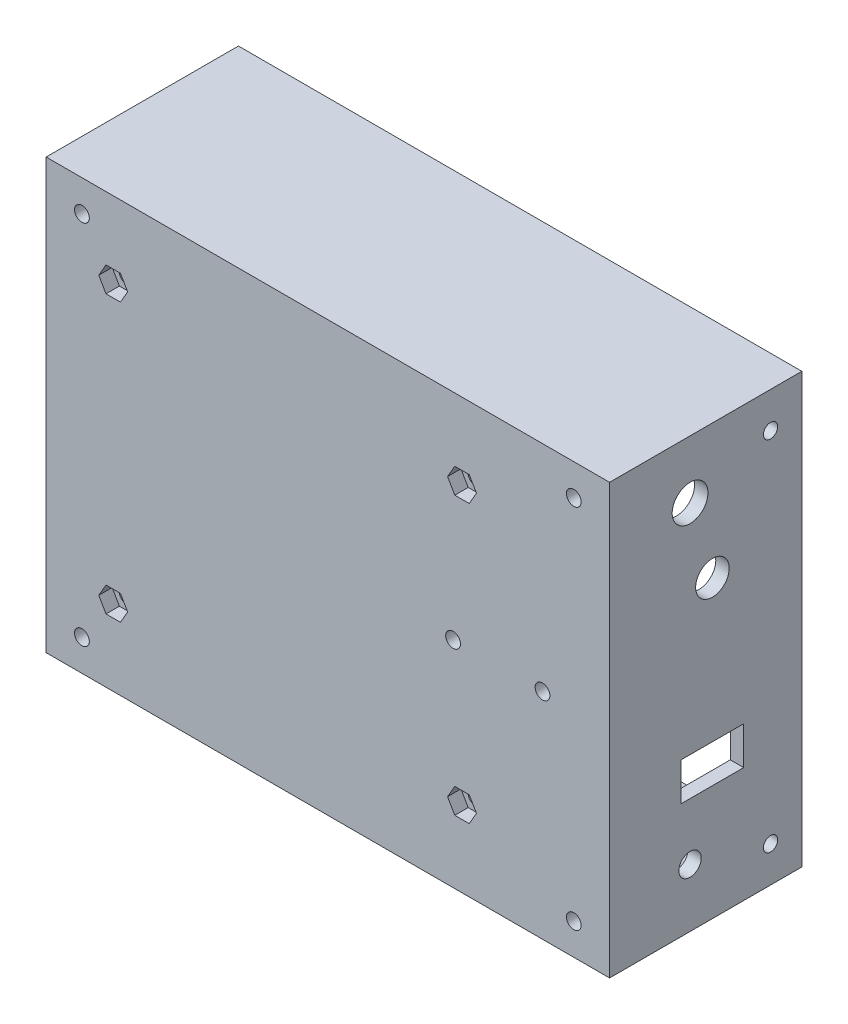
SolidWorks part; units mm, degrees
ref_plane "Front Plane" through (0, 0, 0) normal (0, 0, 1) x (1, 0, 0)
ref_plane "Top Plane" through (0, 0, 0) normal (0, 1, 0) x (1, 0, 0)
ref_plane "Right Plane" through (0, 0, 0) normal (1, 0, 0) x (0, 0, -1)
sketch "Sketch1" plane through (0, 0, 0) normal (0, 0, 1) x (1, 0, 0)
  line L1 (-60, -45) -> (60, -45)
  line L2 (-60, -45) -> (-60, 45)
  line L3 (-60, 45) -> (60, 45)
  line L4 (60, -45) -> (60, 45)
  line L5 (-60, -45) -> (60, 45) construction
  line L6 (-60, 45) -> (60, -45) construction
  line L7 (-48, -31) -> (30, -31)
  line L8 (-48, -31) -> (-48, 31)
  line L9 (-48, 31) -> (30, 31)
  line L10 (30, -31) -> (30, 31)
  line L11 (-48, -31) -> (30, 31) construction
  line L12 (-48, 31) -> (30, -31) construction
  circle A0 centre (-48, 31) radius 1.65
  circle A1 centre (30, 31) radius 1.65
  circle A2 centre (30, -31) radius 1.65
  circle A3 centre (-48, -31) radius 1.65
  circle A4 centre (-55, 41) radius 1.65
  circle A5 centre (55, 41) radius 1.65
  circle A6 centre (55, -41) radius 1.65
  circle A7 centre (-55, -41) radius 1.65
  point P0 (0, 0)
  point P6 (-9, 0)
  dimension "D7" = 3.3
  dimension "D8" = 4
  dimension "D9" = 5
  dimension "D10" = 5
  dimension "D11" = 4
  dimension "D12" = 3.3
  dimension "D13" = 5
  dimension "D14" = 4
  dimension "D15" = 4
  dimension "D16" = 5
  dimension "D1" = 90
  dimension "D2" = 120
  dimension "D3" = 62
  dimension "D4" = 78
  dimension "D5" = 14
  dimension "D6" = 30
extrude "Boss-Extrude2" add sketch "Sketch1" along normal blind 4 contours L1 L4 L3 L2 A3 L8 A0 L9 A1 L10 A2 L7 | A3 L7 A2 L10 A1 L9 A0 L8 region at (-58.5, 0, 0) region at (-9, 0, 0)
sketch "Sketch2" plane through (0, 0, 4) normal (0, 0, 1) x (1, 0, 0)
  line L1 (60, -45) -> (-60, -45)
  line L2 (60, -45) -> (60, 45)
  line L3 (60, 45) -> (-60, 45)
  line L4 (-60, -45) -> (-60, 45)
  line L5 (60, -45) -> (-60, 45) construction
  line L6 (60, 45) -> (-60, -45) construction
  line L7 (63, -48) -> (-63, -48)
  line L8 (63, -48) -> (63, 48)
  line L9 (63, 48) -> (-63, 48)
  line L10 (-63, -48) -> (-63, 48)
  line L11 (63, -48) -> (-63, 48) construction
  line L12 (63, 48) -> (-63, -48) construction
  point P0 (0, 0)
  point P7 (0, 0)
  dimension "D1" = 3
  dimension "D2" = 3
extrude "Boss-Extrude3" add sketch "Sketch2" against normal blind 43
sketch "Sketch3" plane through (-63, 0, 0) normal (-1, 0, 0) x (0, 0, 1)
  line L0 (-39, 48) -> (-39, -48) construction
  line L1 (-39, 48) -> (4, 48) construction
  line L2 (-39, -48) -> (4, -48) construction
  circle A0 centre (-32, -40) radius 1.6
  circle A1 centre (-32, 40) radius 1.6
  dimension "D1" = 3.2
  dimension "D2" = 7
  dimension "D3" = 8
  dimension "D4" = 8
  dimension "D5" = 7
  dimension "D6" = 3.2
extrude "Cut-Extrude1" cut sketch "Sketch3" against normal up to surface (126 mm away) up to face at (63, 0, -17.5)
sketch "Sketch4" plane through (63, 0, 0) normal (1, 0, 0) x (0, 0, -1)
  line L0 (39, -48) -> (39, 48) construction
  line L6 (39, 48) -> (-4, 48) construction
  line L9 (12, -22.25) -> (26, -22.25)
  line L10 (12, -22.25) -> (12, -13.75)
  line L11 (12, -13.75) -> (26, -13.75)
  line L12 (26, -22.25) -> (26, -13.75)
  line L13 (12, -22.25) -> (26, -13.75) construction
  line L14 (12, -13.75) -> (26, -22.25) construction
  line L19 (39, -48) -> (-4, -48) construction
  circle A1 centre (19, 18) radius 3.75
  point P0 (21, 0)
  point P8 (19, -18)
  dimension "D4" = 7.5
  dimension "D5" = 8.5
  dimension "D6" = 20
  dimension "D7" = 14
  dimension "D8" = 30
  dimension "D3" = 30
  dimension "D10" = 20
extrude "Cut-Extrude3" cut sketch "Sketch4" against normal blind 10
sketch "Sketch5" plane through (63, 0, 0) normal (1, 0, 0) x (0, 0, -1)
  line L0 (39, -48) -> (39, 48) construction
  line L1 (39, 48) -> (-4, 48) construction
  circle A0 centre (14, 35) radius 4
  dimension "D1" = 8
  dimension "D2" = 25
  dimension "D3" = 13
extrude "Cut-Extrude4" cut sketch "Sketch5" against normal blind 10
sketch "Sketch6" plane through (63, 0, 0) normal (1, 0, 0) x (0, 0, -1)
  line L0 (22, -35) -> (6, -35)
  line L1 (39, -48) -> (39, 48) construction
  line L3 (39, -48) -> (-4, -48) construction
  line L4 (-4, -48) -> (-4, 48) construction
  circle A0 centre (14, -35) radius 2.5
  point P3 (14, -35)
  dimension "D5" = 5
  dimension "D2" = 25
  dimension "D1" = 16
  dimension "D3" = 13
extrude "Cut-Extrude5" cut sketch "Sketch6" against normal blind 10 contours L0 A0 | A0 region at (63, -36.061, -14)
sketch "Sketch8" plane through (0, 0, 0) normal (0, 0, -1) x (-1, 0, 0)
  line L1 (-60, -45) -> (-60, 45) construction
  circle A0 centre (-48, 0) radius 1.65
  circle A1 centre (-28, 0) radius 1.65
  circle A2 centre (-30, 31) radius 1.65 construction
  dimension "D1" = 3.3
  dimension "D2" = 3.3
  dimension "D3" = 20
  dimension "D4" = 31
  dimension "D5" = 31
  dimension "D6" = 12
extrude "Cut-Extrude6" cut sketch "Sketch8" against normal blind 10
sketch "Sketch9" plane through (0, 0, 0) normal (0, 0, -1) x (-1, 0, 0)
  line L0 (60, -45) -> (-60, -45) construction
  line L1 (-46.3834, 2.8) -> (-49.6166, 2.8)
  line L2 (-49.6166, 2.8) -> (-51.2332, 0)
  line L3 (-51.2332, 0) -> (-49.6166, -2.8)
  line L4 (-49.6166, -2.8) -> (-46.3834, -2.8)
  line L5 (-46.3834, -2.8) -> (-44.7668, 0)
  line L6 (-44.7668, 0) -> (-46.3834, 2.8)
  line L7 (-26.3834, 2.8) -> (-29.6166, 2.8)
  line L8 (-29.6166, 2.8) -> (-31.2332, 0)
  line L9 (-31.2332, 0) -> (-29.6166, -2.8)
  line L10 (-29.6166, -2.8) -> (-26.3834, -2.8)
  line L11 (-26.3834, -2.8) -> (-24.7668, 0)
  line L12 (-24.7668, 0) -> (-26.3834, 2.8)
  line L13 (-45.2287, 4.8) -> (-50.7713, 4.8)
  line L14 (-50.7713, 4.8) -> (-53.5426, 0)
  line L15 (-53.5426, 0) -> (-50.7713, -4.8)
  line L16 (-50.7713, -4.8) -> (-45.2287, -4.8)
  line L17 (-45.2287, -4.8) -> (-42.4574, 0)
  line L18 (-42.4574, 0) -> (-45.2287, 4.8)
  line L19 (-25.2287, 4.8) -> (-30.7713, 4.8)
  line L20 (-30.7713, 4.8) -> (-33.5426, 0)
  line L21 (-33.5426, 0) -> (-30.7713, -4.8)
  line L22 (-30.7713, -4.8) -> (-25.2287, -4.8)
  line L23 (-25.2287, -4.8) -> (-22.4574, 0)
  line L24 (-22.4574, 0) -> (-25.2287, 4.8)
  line L25 (60, -45) -> (-60, -45) construction
  line L26 (-51.7668, 41) -> (-53.3834, 43.8)
  line L27 (-53.3834, 43.8) -> (-56.6166, 43.8)
  line L28 (-56.6166, 43.8) -> (-58.2332, 41)
  line L29 (-58.2332, 41) -> (-56.6166, 38.2)
  line L30 (-56.6166, 38.2) -> (-53.3834, 38.2)
  line L31 (-53.3834, 38.2) -> (-51.7668, 41)
  line L32 (-50.6121, 41) -> (-52.8061, 44.8)
  line L33 (-52.8061, 44.8) -> (-57.1939, 44.8)
  line L34 (-57.1939, 44.8) -> (-59.3879, 41)
  line L35 (-59.3879, 41) -> (-57.1939, 37.2)
  line L36 (-57.1939, 37.2) -> (-52.8061, 37.2)
  line L37 (-52.8061, 37.2) -> (-50.6121, 41)
  line L38 (58.2332, 41) -> (56.6166, 43.8)
  line L39 (56.6166, 43.8) -> (53.3834, 43.8)
  line L40 (53.3834, 43.8) -> (51.7668, 41)
  line L41 (51.7668, 41) -> (53.3834, 38.2)
  line L42 (53.3834, 38.2) -> (56.6166, 38.2)
  line L43 (56.6166, 38.2) -> (58.2332, 41)
  line L44 (52.8061, 44.8) -> (50.6121, 41)
  line L45 (50.6121, 41) -> (52.8061, 37.2)
  line L46 (52.8061, 37.2) -> (57.1939, 37.2)
  line L47 (57.1939, 37.2) -> (59.3879, 41)
  line L48 (59.3879, 41) -> (57.1939, 44.8)
  line L49 (57.1939, 44.8) -> (52.8061, 44.8)
  line L50 (53.3834, -38.2) -> (51.7668, -41)
  line L51 (51.7668, -41) -> (53.3834, -43.8)
  line L52 (53.3834, -43.8) -> (56.6166, -43.8)
  line L53 (56.6166, -43.8) -> (58.2332, -41)
  line L54 (58.2332, -41) -> (56.6166, -38.2)
  line L55 (56.6166, -38.2) -> (53.3834, -38.2)
  line L56 (50.6121, -41) -> (52.8061, -44.8)
  line L57 (52.8061, -44.8) -> (57.1939, -44.8)
  line L58 (57.1939, -44.8) -> (59.3879, -41)
  line L59 (59.3879, -41) -> (57.1939, -37.2)
  line L60 (57.1939, -37.2) -> (52.8061, -37.2)
  line L61 (52.8061, -37.2) -> (50.6121, -41)
  line L62 (-53.3834, -38.2) -> (-56.6166, -38.2)
  line L63 (-56.6166, -38.2) -> (-58.2332, -41)
  line L64 (-58.2332, -41) -> (-56.6166, -43.8)
  line L65 (-56.6166, -43.8) -> (-53.3834, -43.8)
  line L66 (-53.3834, -43.8) -> (-51.7668, -41)
  line L67 (-51.7668, -41) -> (-53.3834, -38.2)
  line L68 (-52.8061, -37.2) -> (-57.1939, -37.2)
  line L69 (-57.1939, -37.2) -> (-59.3879, -41)
  line L70 (-59.3879, -41) -> (-57.1939, -44.8)
  line L71 (-57.1939, -44.8) -> (-52.8061, -44.8)
  line L72 (-52.8061, -44.8) -> (-50.6121, -41)
  line L73 (-50.6121, -41) -> (-52.8061, -37.2)
  circle A0 centre (-48, 0) radius 2.8 construction
  circle A1 centre (-28, 0) radius 2.8 construction
  circle A2 centre (-48, 0) radius 4.8 construction
  circle A3 centre (-28, 0) radius 4.8 construction
  circle A4 centre (-55, 41) radius 2.8 construction
  circle A5 centre (-55, 41) radius 3.8 construction
  circle A6 centre (55, 41) radius 2.8 construction
  circle A7 centre (55, 41) radius 3.8 construction
  circle A8 centre (55, -41) radius 2.8 construction
  circle A9 centre (55, -41) radius 3.8 construction
  circle A10 centre (-55, -41) radius 2.8 construction
  circle A11 centre (-55, -41) radius 3.8 construction
  dimension "D1" = 5.6
  dimension "D2" = 2
  dimension "D3" = 5.6
  dimension "D4" = 1
extrude "Boss-Extrude4" add sketch "Sketch9" along normal blind 3
sketch "Sketch10" plane through (0, 0, 4) normal (0, 0, 1) x (1, 0, 0)
  line L0 (63, 48) -> (-63, 48) construction
  line L1 (-44.7668, 31) -> (-46.3834, 33.8)
  line L2 (-46.3834, 33.8) -> (-49.6166, 33.8)
  line L3 (-49.6166, 33.8) -> (-51.2332, 31)
  line L4 (-51.2332, 31) -> (-49.6166, 28.2)
  line L5 (-49.6166, 28.2) -> (-46.3834, 28.2)
  line L6 (-46.3834, 28.2) -> (-44.7668, 31)
  line L7 (33.2332, 31) -> (31.6166, 33.8)
  line L8 (31.6166, 33.8) -> (28.3834, 33.8)
  line L9 (28.3834, 33.8) -> (26.7668, 31)
  line L10 (26.7668, 31) -> (28.3834, 28.2)
  line L11 (28.3834, 28.2) -> (31.6166, 28.2)
  line L12 (31.6166, 28.2) -> (33.2332, 31)
  line L25 (-44.7668, -31) -> (-46.3834, -28.2)
  line L26 (-46.3834, -28.2) -> (-49.6166, -28.2)
  line L27 (-49.6166, -28.2) -> (-51.2332, -31)
  line L28 (-51.2332, -31) -> (-49.6166, -33.8)
  line L29 (-49.6166, -33.8) -> (-46.3834, -33.8)
  line L30 (-46.3834, -33.8) -> (-44.7668, -31)
  line L31 (33.2332, -31) -> (31.6166, -28.2)
  line L32 (31.6166, -28.2) -> (28.3834, -28.2)
  line L33 (28.3834, -28.2) -> (26.7668, -31)
  line L34 (26.7668, -31) -> (28.3834, -33.8)
  line L35 (28.3834, -33.8) -> (31.6166, -33.8)
  line L36 (31.6166, -33.8) -> (33.2332, -31)
  circle A0 centre (-48, 31) radius 2.8 construction
  circle A1 centre (30, 31) radius 2.8 construction
  circle A4 centre (-48, -31) radius 2.8 construction
  circle A5 centre (30, -31) radius 2.8 construction
  dimension "D2" = 5.6
extrude "Cut-Extrude8" cut sketch "Sketch10" against normal blind 3
sketch "Sketch12" plane through (0, 0, 0) normal (0, 0, -1) x (-1, 0, 0)
  circle A0 centre (-30, 31) radius 1.65
  circle A1 centre (48, 31) radius 1.65
  circle A2 centre (48, -31) radius 1.65
  circle A3 centre (-30, -31) radius 1.65
  circle A4 centre (-30, -31) radius 4
  circle A5 centre (48, -31) radius 4
  circle A6 centre (48, 31) radius 4
  circle A7 centre (-30, 31) radius 4
  dimension "D1" = 8
extrude "Boss-Extrude11" add sketch "Sketch12" along normal blind 5
sketch "Sketch13" plane through (60, 0, 0) normal (-1, 0, 0) x (0, 0, 1)
  line L1 (-19, 29) -> (-9, 29)
  line L2 (-19, 29) -> (-19, 41)
  line L3 (-19, 41) -> (-9, 41)
  line L4 (-9, 29) -> (-9, 41)
  line L5 (-19, 29) -> (-9, 41) construction
  line L6 (-19, 41) -> (-9, 29) construction
  line L7 (-22, 27) -> (-6, 27)
  line L8 (-22, 27) -> (-22, 43)
  line L9 (-22, 43) -> (-6, 43)
  line L10 (-6, 27) -> (-6, 43)
  line L11 (-22, 27) -> (-6, 43) construction
  line L12 (-22, 43) -> (-6, 27) construction
  point P0 (-14, 35)
  point P6 (-14, 35)
  dimension "D1" = 12
  dimension "D2" = 10
  dimension "D3" = 2
  dimension "D4" = 3
extrude "Boss-Extrude12" add sketch "Sketch13" along normal blind 1
chamfer "Chamfer1" distance 1 angle 45 2 edges at (59, 35, -6) (59, 35, -22)
sketch "Sketch16" plane through (0, 0, 0) normal (0, 0, -1) x (-1, 0, 0)
  line L0 (-50.6121, 42) -> (44, 42)
  line L1 (44, 42) -> (44, 30.25)
  line L2 (47.25, 27) -> (57, 27)
  line L3 (57, 27) -> (57, -27)
  line L4 (57, -27) -> (47.25, -27)
  line L5 (44, -30.25) -> (44, -42)
  line L6 (44, -42) -> (-50.6121, -42)
  line L7 (-50.6121, -42) -> (-50.6121, -37.2)
  line L8 (-50.6121, -37.2) -> (-57, -37.2)
  line L9 (-57, -37.2) -> (-57, 37.2)
  line L10 (-57, 37.2) -> (-50.6121, 37.2)
  line L11 (-50.6121, 37.2) -> (-50.6121, 42)
  line L12 (-57, 4.8) -> (-22.4574, 4.8)
  line L13 (-22.4574, 4.8) -> (-22.4574, -4.8)
  line L14 (-22.4574, -4.8) -> (-57, -4.8)
  line L15 (-22.4574, 1.5) -> (57, 1.5)
  line L16 (57, 1.5) -> (57, -1.5)
  line L17 (57, -1.5) -> (-22.4574, -1.5)
  line L18 (-60, 45) -> (-60, -45)
  line L19 (60, -45) -> (-60, -45) construction
  line L20 (-60, -45) -> (-60, 45) construction
  line L21 (-60, -45) -> (60, -45)
  line L22 (60, -45) -> (60, 45)
  line L23 (60, 45) -> (-60, 45)
  line L24 (-1.5, 42) -> (-1.5, -42)
  line L25 (-1.5, -42) -> (1.5, -42)
  line L26 (1.5, -42) -> (1.5, 42)
  line L27 (1.5, 42) -> (-1.5, 42)
  line L28 (-45.2287, 4.8) -> (-50.7713, 4.8) construction
  line L29 (-50.7713, -4.8) -> (-45.2287, -4.8) construction
  line L30 (-60, -45) -> (-60, 45) construction
  line L31 (-52.8061, -37.2) -> (-57.1939, -37.2) construction
  line L32 (-57.1939, 37.2) -> (-52.8061, 37.2) construction
  line L33 (-50.6121, 41) -> (-52.8061, 37.2)
  line L34 (-52.8061, -37.2) -> (-50.6121, -41)
  line L35 (-22.4574, -1.5) -> (-24.3627, -4.8)
  line L36 (-24.3627, 4.8) -> (-22.4574, 1.5)
  line L37 (-22.4574, 0) -> (-25.2287, 4.8) construction
  line L38 (-25.2287, -4.8) -> (-22.4574, 0) construction
  circle A0 centre (48, -31) radius 4 construction
  circle A1 centre (48, 31) radius 4 construction
  arc A2 (47.25, -27) -> (44, -30.25) centre (47.25, -30.25) ccw
  arc A3 (44, 30.25) -> (47.25, 27) centre (47.25, 30.25) ccw
  circle M27 centre (-30, -31) radius 4
  line M34 (-45.2287, -4.8) -> (-50.7713, -4.8)
  line M37 (-50.7713, 4.8) -> (-45.2287, 4.8)
  line M40 (-25.2287, -4.8) -> (-30.7713, -4.8)
  line M43 (-30.7713, 4.8) -> (-25.2287, 4.8)
  line M44 (-50.6121, 41) -> (-52.8061, 37.2)
  line M45 (-52.8061, 37.2) -> (-57.1939, 37.2)
  line M54 (52.8061, 37.2) -> (50.6121, 41)
  line M55 (50.6121, 41) -> (52.8061, 44.8)
  line M56 (50.6121, -41) -> (52.8061, -37.2)
  line M61 (52.8061, -44.8) -> (50.6121, -41)
  line M62 (-52.8061, -37.2) -> (-50.6121, -41)
  line M67 (-57.1939, -37.2) -> (-52.8061, -37.2)
  circle M69 centre (-30, 31) radius 4
  dimension "D9" = 3.25
  dimension "D1" = 3
  dimension "D2" = 3
  dimension "D3" = 3
  dimension "D4" = 1.5
  dimension "D5" = 1.5
  dimension "D6" = 3
  dimension "D7" = 3
  dimension "D8" = 3
extrude "Cut-Extrude11" cut sketch "Sketch16" against normal blind 3 contours L24 L0 L11 L10 L9 L12 L13 L15 M45 M37 M43 M69 | L26 L15 L3 L2 L1 L0 M54 M55 | L26 L6 L5 L4 L3 L17 M61 M56 | L24 L17 L13 L14 L9 L8 L7 L6 M40 M34 M67 M27 | L7 L8 M62 | L10 L11 M44 | L12 L36 L13 | L13 L35 L14 region at (28.283, 22.2897, 0) region at (51.3434, 38.4667, 0) region at (-27.2507, 20.5467, 0) region at (23.0925, 3.7, 0) region at (28.283, -22.2897, 0) region at (-27.2507, -20.5467, 0) region at (23.0925, -3.7, 0) region at (51.3434, -38.4667, 0)
sketch "Sketch17" plane through (0, 45, 0) normal (0, -1, 0) x (1, 0, 0)
  line L1 (-57, -36) -> (57, -36)
  line L2 (-57, -36) -> (-57, -3)
  line L3 (-57, -3) -> (57, -3)
  line L4 (57, -36) -> (57, -3)
  line L5 (-60, 0) -> (60, 0) construction
  line L6 (60, -39) -> (60, 0) construction
  line L7 (-60, -39) -> (-60, 0) construction
  line L8 (60, -39) -> (-60, -39) construction
  line L9 (-1.5, 3) -> (-1.5, 0) construction
  line L10 (-57, -18) -> (57, -18)
  line L11 (-57, -18) -> (-57, -21)
  line L12 (-57, -21) -> (57, -21)
  line L13 (57, -18) -> (57, -21)
  line L14 (-1.5, -3) -> (1.5, -3)
  line L15 (-1.5, -3) -> (-1.5, -36)
  line L16 (-1.5, -36) -> (1.5, -36)
  line L17 (1.5, -3) -> (1.5, -36)
  dimension "D1" = 3
  dimension "D2" = 3
  dimension "D3" = 3
  dimension "D4" = 3
  dimension "D5" = 3
  dimension "D6" = 3
  dimension "D7" = 15
extrude "Cut-Extrude13" cut sketch "Sketch17" against normal blind 2 contours L15 L12 L2 L1 | L15 L3 L2 L10 | L3 L17 L10 L4 | L12 L17 L1 L4 region at (-29.25, 45, -28.5) region at (29.25, 45, -28.5) region at (-29.25, 45, -10.5) region at (29.25, 45, -10.5)
sketch "Sketch20" plane through (0, -45, 0) normal (0, 1, 0) x (1, 0, 0)
  line L0 (-57, -3) -> (-57, 0) construction
  line L1 (-57, 36) -> (57, 36)
  line L2 (-57, 36) -> (-57, 3)
  line L3 (-57, 3) -> (57, 3)
  line L4 (57, 36) -> (57, 3)
  line L5 (-1.5, 36) -> (1.5, 36)
  line L6 (-1.5, 36) -> (-1.5, 3)
  line L7 (-1.5, 3) -> (1.5, 3)
  line L8 (1.5, 36) -> (1.5, 3)
  line L9 (-57, 21) -> (57, 21)
  line L10 (-57, 21) -> (-57, 18)
  line L11 (-57, 18) -> (57, 18)
  line L12 (57, 21) -> (57, 18)
  line L13 (57, -3) -> (57, 0) construction
  line L14 (1.5, 36) -> (57, 36) construction
  line L16 (-57, 21) -> (-1.5, 21) construction
  line L17 (-57, 3) -> (-1.5, 3) construction
  line L18 (1.5, 21) -> (57, 21) construction
  line L19 (-57, 18) -> (-1.5, 18) construction
  line L20 (-1.5, 3) -> (-1.5, 18) construction
  line L21 (1.5, 3) -> (1.5, 18) construction
extrude "Cut-Extrude14" cut sketch "Sketch20" against normal blind 2 contours L2 L9 L6 L1 | L8 L9 L4 L1 | L11 L8 L3 L4 | L11 L2 L3 L6 region at (-29.25, -45, -28.5) region at (29.25, -45, -28.5) region at (-29.25, -45, -10.5) region at (29.25, -45, -10.5)
sketch "Sketch21" plane through (-60, 0, 0) normal (1, 0, 0) x (0, 0, -1)
  line L0 (0, -45) -> (0, 45) construction
  line L1 (28, 42) -> (3, 42)
  line L2 (28, 42) -> (28, -42)
  line L3 (28, -42) -> (3, -42)
  line L4 (3, 42) -> (3, -42)
  line L5 (28, 36) -> (36, 36)
  line L6 (28, 36) -> (28, -36)
  line L7 (28, -36) -> (36, -36)
  line L8 (36, 36) -> (36, -36)
  line L9 (3, 1.5) -> (36, 1.5)
  line L10 (3, 1.5) -> (3, -1.5)
  line L11 (3, -1.5) -> (36, -1.5)
  line L12 (36, 1.5) -> (36, -1.5)
  line L13 (21, 42) -> (18, 42)
  line L14 (21, 42) -> (21, -42)
  line L15 (21, -42) -> (18, -42)
  line L16 (18, 42) -> (18, -42)
  line L17 (39, 45) -> (0, 45) construction
  line L18 (39, 45) -> (39, -45) construction
  line L19 (39, -45) -> (0, -45) construction
  line L20 (-3, -1.5) -> (0, -1.5) construction
  dimension "D1" = 3
  dimension "D2" = 3
  dimension "D3" = 3
  dimension "D4" = 3
  dimension "D5" = 6
  dimension "D6" = 6
  dimension "D7" = 8
  dimension "D8" = 3
  dimension "D9" = 3
  dimension "D10" = 15
extrude "Cut-Extrude15" cut sketch "Sketch21" against normal blind 2 contours L2 L9 L8 L5 | L1 L14 L9 L2 | L11 L2 L7 L8 | L11 L14 L3 L2 | L16 L11 L4 L3 | L16 L1 L4 L9 region at (-60, 21.75, -24.5) region at (-60, 18.75, -32) region at (-60, 21.75, -10.5) region at (-60, -21.75, -24.5) region at (-60, -18.75, -32) region at (-60, -21.75, -10.5)
chamfer "Chamfer6" distance 1.5 angle 45 14 edges at (29.25, -47, -18) (29.25, -47, -36) (-29.25, -47, -36) (-29.25, -47, -18) (-62, 21.75, -18) (-62, -21.75, -18) (-62, -39, -28) (-62, -18.75, -36) (-62, 39, -28) (-62, 18.75, -36) (-29.25, 47, -18) (29.25, 47, -18) (-29.25, 47, -36) (29.25, 47, -36)
